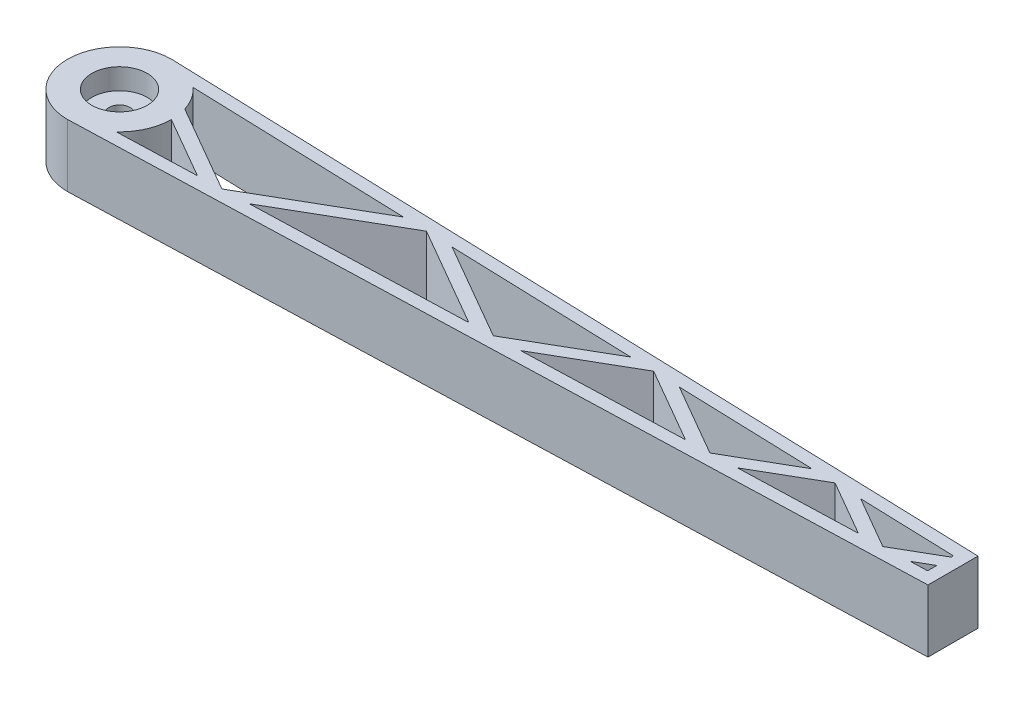
SolidWorks part; units mm, degrees
ref_plane "Front Plane" through (0, 0, 0) normal (0, 0, 1) x (1, 0, 0)
ref_plane "Top Plane" through (0, 0, 0) normal (0, 1, 0) x (1, 0, 0)
ref_plane "Right Plane" through (0, 0, 0) normal (1, 0, 0) x (0, 0, -1)
sketch "Sketch1" plane through (0, 0, 0) normal (0, 1, 0) x (1, 0, 0)
  line L0 (200, -6) -> (200, 6)
  line L1 (200, 6) -> (0, 12.5)
  line L2 (200, -6) -> (0, -12.5)
  line L3 (8.4358, 9.2243) -> (60.6202, 7.5283)
  line L4 (8.4358, -9.2243) -> (27.3057, -8.611)
  line L5 (197, 3.0959) -> (197, 2.5702)
  line L6 (32.986, -8.4264) -> (60.6202, 7.5283)
  line L7 (0, 0) -> (47.5809, 0) construction
  line L8 (39.3439, -8.2197) -> (66.3005, 7.3437)
  line L9 (32.986, -8.4264) -> (11.9305, 3.73)
  line L10 (66.3005, 7.3437) -> (90.3839, -6.5609)
  line L11 (72.6584, 7.137) -> (96.0642, -6.3763)
  line L12 (27.3057, -8.611) -> (12.4998, -0.0628)
  line L13 (96.0642, -6.3763) -> (116.9753, 5.6967)
  line L14 (102.4221, -6.1697) -> (122.6556, 5.5121)
  line L15 (122.6556, 5.5121) -> (140.7325, -4.9246)
  line L16 (129.0135, 5.3055) -> (146.4127, -4.74)
  line L17 (146.4127, -4.74) -> (161.9575, 4.2348)
  line L18 (152.7706, -4.5334) -> (167.6378, 4.0502)
  line L19 (167.6378, 4.0502) -> (180.9204, -3.6185)
  line L20 (173.9957, 3.8436) -> (186.6006, -3.4339)
  line L21 (186.6006, -3.4339) -> (197, 2.5702)
  line L22 (192.9585, -3.2273) -> (197, -0.8939)
  line L23 (197, -0.8939) -> (197, -3.0959)
  line L24 (173.9957, 3.8436) -> (197, 3.0959)
  line L25 (192.9585, -3.2273) -> (197, -3.0959)
  line L26 (180.6529, 0) -> (192.5483, 0) construction
  line L27 (160.6227, 0) -> (174.6529, 0) construction
  line L28 (152.7706, -4.5334) -> (180.9204, -3.6185)
  line L29 (129.0135, 5.3055) -> (161.9575, 4.2348)
  line L30 (138.2028, 0) -> (154.6227, 0) construction
  line L31 (113.1083, 0) -> (132.2028, 0) construction
  line L32 (102.4221, -6.1697) -> (140.7325, -4.9246)
  line L33 (85.02, 0) -> (107.1083, 0) construction
  line L34 (72.6584, 7.137) -> (116.9753, 5.6967)
  line L35 (53.5809, 0) -> (79.02, 0) construction
  line L36 (39.3439, -8.2197) -> (90.3839, -6.5609)
  circle A0 centre (0, 0) radius 6.65
  arc A1 (0, 12.5) -> (0, -12.5) centre (0, 0) ccw
  arc A2 (8.4358, -9.2243) -> (12.5, 0) centre (0, 0) ccw
  arc A3 (11.9305, 3.73) -> (8.4358, 9.2243) centre (0, 0) ccw
  point P6 (200, 0)
  dimension "D1" = 13.3
  dimension "D4" = 25
  dimension "D2" = 12
  dimension "D3" = 200
  dimension "D5" = 3
  dimension "D6" = 3
  dimension "D7" = 3
  dimension "D8" = 150
  dimension "D9" = 150
  dimension "D10" = 3
  dimension "D11" = 3
  dimension "D12" = 3
  dimension "D13" = 3
  dimension "D14" = 3
  dimension "D15" = 3
  dimension "D16" = 3
  dimension "D17" = 3
extrude "Boss-Extrude1" add sketch "Sketch1" along normal blind 15 contours L1 A1 L2 L0 L11 L34 L13 L16 L29 L17 L20 L24 L5 L21 L25 L22 L23 L28 L18 L19 L32 L14 L15 L36 L8 L10 A0 L4 A2 L12 L9 A3 L3 L6 region at (99.9305, 0, 7.1115)
ref_plane "Plane1" through (0, 10, 0) normal (0, 1, 0) x (1, 0, 0)
sketch "Sketch2" plane through (0, 10, 0) normal (0, 1, 0) x (1, 0, 0)
  circle A0 centre (0, 0) radius 6.65
  circle A1 centre (0, 0) radius 2.5
  dimension "D1" = 5
extrude "Boss-Extrude2" add sketch "Sketch2" against normal blind 5
